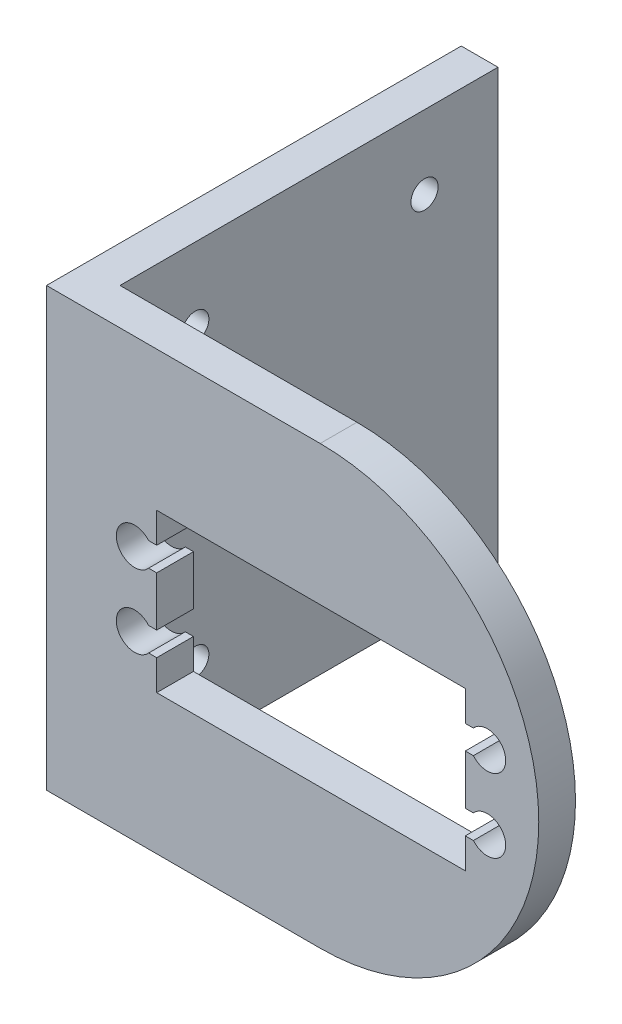
SolidWorks part; units mm, degrees
ref_plane "Front Plane" through (0, 0, 0) normal (0, 0, 1) x (1, 0, 0)
ref_plane "Top Plane" through (0, 0, 0) normal (0, 1, 0) x (1, 0, 0)
ref_plane "Right Plane" through (0, 0, 0) normal (1, 0, 0) x (0, 0, -1)
sketch "Sketch1" plane through (0, 0, 0) normal (0, 0, 1) x (1, 0, 0)
  line L0 (-20, -5.1351) -> (-20, -49991.25) construction
  line L1 (-27.5, 0) -> (-31, 0) construction
  line L2 (-22.1002, 6.625) -> (-21, 6.625)
  line L3 (-27.5, -3.375) -> (-27.5, 3.375) construction
  line L4 (-22.1002, 3.375) -> (-21, 3.375)
  line L5 (-25.8998, 6.625) -> (-27.5, 6.625) construction
  line L6 (-25.8998, 3.375) -> (-27.5, 3.375) construction
  line L7 (-21, 3.375) -> (-21, -3.375)
  line L8 (-22.1002, -3.375) -> (-21, -3.375)
  line L9 (-31, 29.75) -> (-21, 29.75)
  line L10 (-31, 29.75) -> (-31, -29.75)
  line L11 (-31, -29.75) -> (-21, -29.75)
  line L12 (-21, 10.75) -> (-21, 6.625)
  line L13 (-22.1002, -6.625) -> (-21, -6.625)
  line L14 (-21, -6.625) -> (-21, -10.75)
  line L15 (-26.5, 9.75) -> (-19, 9.75) construction
  line L16 (0, 0) -> (0, 50000) construction
  line L17 (27.5, 0) -> (31, 0) construction
  line L18 (21, -6.625) -> (21, -10.75)
  line L19 (22.1002, -6.625) -> (21, -6.625)
  line L20 (21.0358, 10.75) -> (21, 6.625)
  line L21 (31, -29.75) -> (21, -29.75)
  line L22 (31, 29.75) -> (31, -29.75)
  line L23 (31, 29.75) -> (21, 29.75)
  line L24 (22.1002, -3.375) -> (21, -3.375)
  line L25 (21, 3.375) -> (21, -3.375)
  line L26 (22.1002, 3.375) -> (21, 3.375)
  line L27 (22.1002, 6.625) -> (21, 6.625)
  line L28 (-21, 10.75) -> (21.0358, 10.75)
  line L29 (-21, -10.75) -> (21, -10.75)
  line L30 (-19, 9.75) -> (19, 9.75) construction
  line L31 (-21, -29.75) -> (21, -29.75)
  line L32 (-21, 29.75) -> (21, 29.75)
  arc A0 (-22.1002, 6.625) -> (-22.1002, 3.375) centre (-24, 5) ccw
  arc A1 (-25.8998, 3.375) -> (-25.8998, 6.625) centre (-24, 5) ccw construction
  arc A2 (-22.1002, -6.625) -> (-22.1002, -3.375) centre (-24, -5) cw
  arc A3 (22.1002, -6.625) -> (22.1002, -3.375) centre (24, -5) ccw
  arc A4 (22.1002, 6.625) -> (22.1002, 3.375) centre (24, 5) cw
  dimension "D3" = 20
  dimension "D1" = 1
  dimension "D2" = 10
  dimension "D4" = 1
extrude "Boss-Extrude1" add sketch "Sketch1" along normal blind 5
sketch "Sketch2" plane through (0, 0, -51.7) normal (0, 0, -1) x (-1, 0, 0)
  line L0 (31, 29.75) -> (31, -29.75) construction
  line L1 (-31, 29.75) -> (31, 29.75) construction
  line L2 (31, -29.75) -> (-31, -29.75) construction
  line L3 (-31, -29.75) -> (-31, 29.75) construction
  line L4 (31, 29.75) -> (31, -29.75)
  line L5 (-31, 29.75) -> (31, 29.75)
  line L6 (31, -29.75) -> (-31, -29.75)
  line L7 (-31, -29.75) -> (-31, 29.75)
  circle A0 centre (-10, 0) radius 12.375 construction
  circle A1 centre (-10, 0) radius 12.375 construction
  circle A2 centre (-10, 0) radius 12.75
  dimension "D1" = 0.375
extrude "Boss-Extrude2" [suppressed] add sketch "Sketch2" along normal blind 5 separate body
sketch "Sketch3" plane through (-31, 0, 0) normal (-1, 0, 0) x (0, 0, 1)
  line L0 (5, 29.75) -> (-51.45, 29.75)
  line L1 (5, 29.75) -> (5, -29.75)
  line L2 (5, -29.75) -> (-51.45, -29.75)
  line L3 (-51.45, -29.75) -> (-51.45, 29.75)
  line L6 (-25.85, -29.75) -> (-25.85, 29.75) construction
  line L8 (-25.85, 0) -> (-50025.85, 0) construction
  line L9 (0, 29.75) -> (0, -29.75) construction
  line L10 (-51.7, -29.75) -> (-51.7, 29.75) construction
  circle A0 centre (-41.45, 19.75) radius 1.85
  circle A1 centre (-41.45, -19.75) radius 1.85
  circle A2 centre (-10.25, -19.75) radius 1.85
  circle A3 centre (-10.25, 19.75) radius 1.85
  point P16 (-25.85, 0)
  dimension "D2" = 10
  dimension "D4" = 3.7
  dimension "D1" = 0.25
  dimension "D3" = 10
extrude "Boss-Extrude3" add sketch "Sketch3" along normal blind 5
fillet "Fillet2" 2 edges at (31, 29.75, 2.5) (31, -29.75, 2.5) type full round first side face at (-6.8333, 29.75, -11.1958) second side face at (-17.1667, -29.75, -19.7708) middle face at (31, 0, 2.5)
